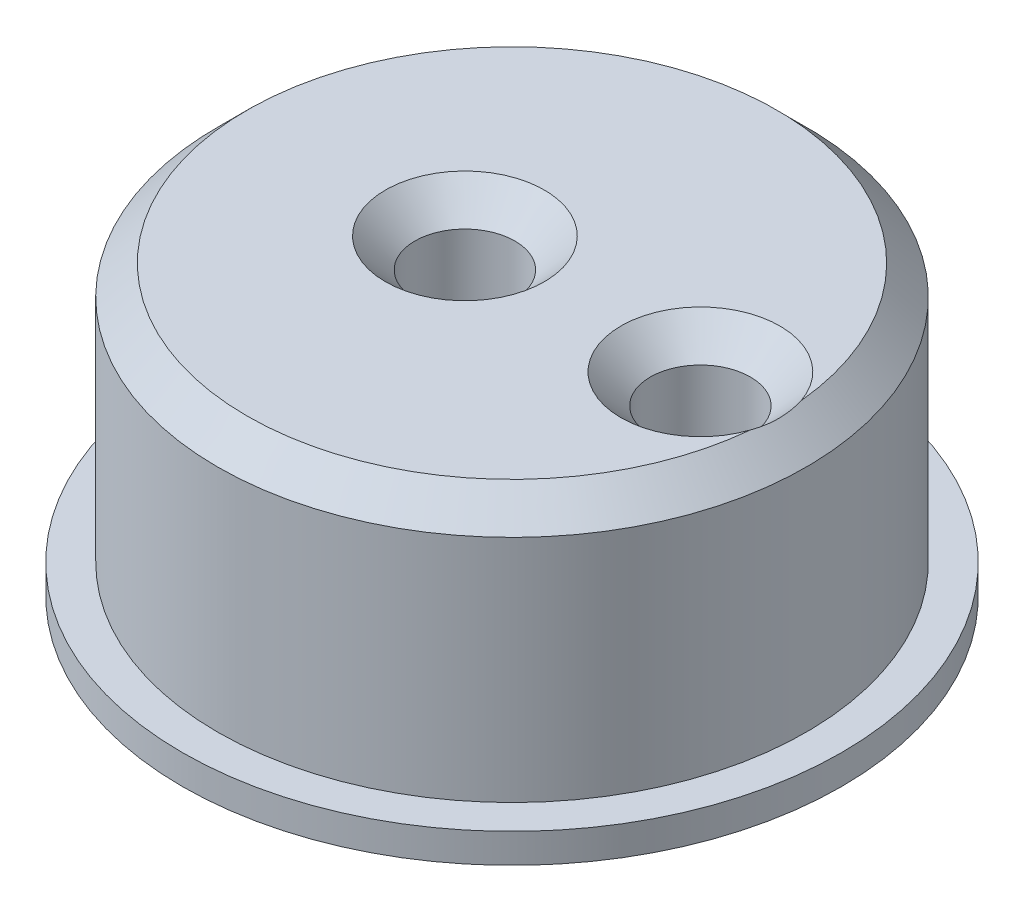
SolidWorks part; units mm, degrees
ref_plane "前视基准面" through (0, 0, 0) normal (0, 0, 1) x (1, 0, 0)
ref_plane "上视基准面" through (0, 0, 0) normal (0, 1, 0) x (1, 0, 0)
ref_plane "右视基准面" through (0, 0, 0) normal (1, 0, 0) x (0, 0, -1)
other "Configuration Table"
sketch "草图1" plane through (0, 0, 0) normal (0, 1, 0) x (1, 0, 0)
  line L0 (1.2, 6.4178) -> (1.2, -6.4114) construction
  line L1 (-5.7349, 0) -> (5.8104, 0) construction
  circle A0 centre (0, 0) radius 5
  circle A1 centre (3.2, 0) radius 0.85
  circle A2 centre (-0.8, 0) radius 0.85
  dimension "D1" = 10
  dimension "D3" = 4
  dimension "D4" = 1.7
  dimension "D2" = 1.2
extrude "凸台-拉伸1" add sketch "草图1" along normal blind 4.4
sketch "草图3" plane through (0, 0, 0) normal (0, -1, 0) x (1, 0, 0)
  circle A0 centre (3.2, 0) radius 0.85 construction
  circle A1 centre (0, 0) radius 5 construction
  circle A3 centre (-0.8, 0) radius 0.85 construction
  circle A4 centre (3.2, 0) radius 0.85
  circle A5 centre (-0.8, 0) radius 0.85
  circle A6 centre (0, 0) radius 5 construction
  circle A7 centre (0, 0) radius 5.6
  dimension "D1" = 0.6
extrude "凸台-拉伸2" add sketch "草图3" along normal blind 0.5
chamfer "倒角1" distance 0.5 angle 45 5 edges at (0, 4.4, 5) (-0.8, 4.4, -0.85) (3.2, 4.4, 0.85) (-0.8, -0.5, -0.85) (3.2, -0.5, -0.85)
ref_axis "基准轴1" through (0, 4, 0) along (0, -1, 0)
sketch "草图2" plane through (0, 0, 0) normal (0, 1, 0) x (1, 0, 0)
  line L0 (-5.9042, 0) -> (6.2358, 0) construction
